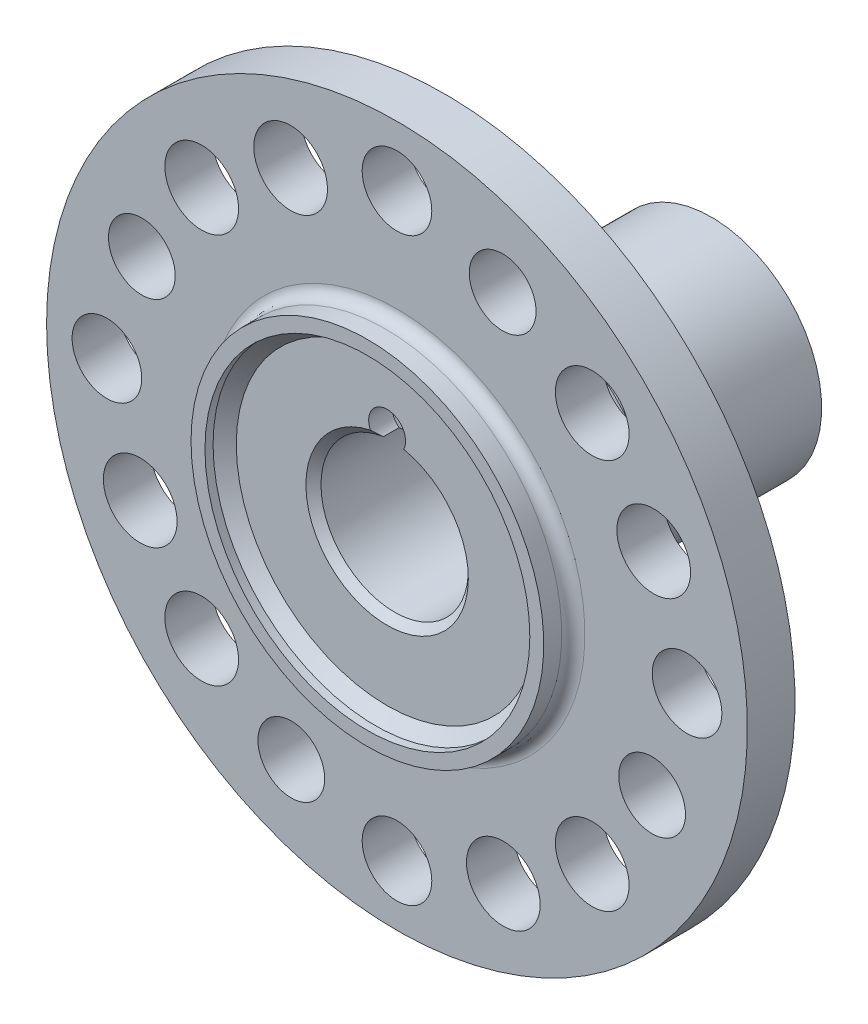
SolidWorks part; units mm, degrees
material "AISI 4130 Steel, normalized at 870C"
ref_plane "Front Plane" through (0, 0, 0) normal (0, 0, 1) x (1, 0, 0)
ref_plane "Top Plane" through (0, 0, 0) normal (0, 1, 0) x (1, 0, 0)
ref_plane "Right Plane" through (0, 0, 0) normal (1, 0, 0) x (0, 0, -1)
sketch "Sketch1" plane through (0, 0, 0) normal (1, 0, 0) x (0, 0, -1)
  line L0 (0.5, 19) -> (38, 19)
  line L1 (38, 19) -> (38, 18)
  line L2 (38, 18) -> (34.1, 14.1)
  line L3 (34.1, 14.1) -> (18.3, 14.1)
  line L4 (18.3, 14.1) -> (16.9, 12.7)
  line L5 (16.9, 12.7) -> (-16.6, 12.7)
  line L6 (-16.6, 12.7) -> (-17.9, 14)
  line L7 (-17.9, 14) -> (-17.9, 20.7)
  line L8 (0, 19.5) -> (0, 25.25)
  line L9 (0, 25.25) -> (-3.6, 28.85)
  line L10 (-3.6, 28.85) -> (-3.6, 35.7)
  line L11 (-3.6, 35.7) -> (-5.45, 35.7)
  line L12 (-7.45, 37.7) -> (-7.45, 38.8)
  line L13 (-7.45, 38.8) -> (-7.5, 38.8)
  line L14 (-8, 39.3) -> (-8, 60.4)
  line L15 (-8, 60.4) -> (-16.2, 60.4)
  line L16 (-16.2, 60.4) -> (-16.2, 32.4)
  line L17 (-18.2, 30.4) -> (-21.3, 30.4)
  line L18 (-21.3, 30.4) -> (-21.3, 29.9)
  line L19 (-23.3, 27.9) -> (-27.5, 27.9)
  line L20 (-27.5, 27.9) -> (-27.5, 25.3)
  line L21 (-27.5, 25.3) -> (-22.3, 25.3)
  line L22 (-20.3, 23.3) -> (-20.3, 21.7)
  line L23 (-20.3, 21.7) -> (-18.9, 21.7)
  line L25 (0, 0) -> (-74.9273, 0) construction
  arc A0 (0.5, 19) -> (0, 19.5) centre (0.5, 19.5) cw
  arc A1 (-5.45, 35.7) -> (-7.45, 37.7) centre (-5.45, 37.7) cw
  arc A2 (-7.5, 38.8) -> (-8, 39.3) centre (-7.5, 39.3) cw
  arc A3 (-22.3, 25.3) -> (-20.3, 23.3) centre (-22.3, 23.3) cw
  arc A4 (-21.3, 29.9) -> (-23.3, 27.9) centre (-23.3, 29.9) cw
  arc A5 (-16.2, 32.4) -> (-18.2, 30.4) centre (-18.2, 32.4) cw
  arc A6 (-18.9, 21.7) -> (-17.9, 20.7) centre (-18.9, 20.7) cw
  point P30 (0, 19)
  point P39 (-21.3, 27.9)
  dimension "D25" = 0.5
  dimension "D26" = 2
  dimension "D27" = 0.5
  dimension "D28" = 2
  dimension "D29" = 1
  dimension "D1" = 120.8
  dimension "D2" = 38
  dimension "D3" = 1
  dimension "D4" = 28.2
  dimension "D5" = 45
  dimension "D6" = 15.8
  dimension "D7" = 25.4
  dimension "D8" = 38
  dimension "D9" = 50.5
  dimension "D10" = 3.6
  dimension "D11" = 71.4
  dimension "D12" = 0.55
  dimension "D13" = 77.6
  dimension "D14" = 4.4
  dimension "D15" = 8.2
  dimension "D16" = 55.8
  dimension "D17" = 60.8
  dimension "D18" = 65.5
  dimension "D19" = 6.2
  dimension "D20" = 28
  dimension "D21" = 2.6
  dimension "D22" = 9.6
  dimension "D23" = 7.2
  dimension "D24" = 43.4
revolve "Revolve1" add sketch "Sketch1" angle 360 about L25
sketch "Sketch11" plane through (0, 0, 0) normal (0, 0, 1) x (1, 0, 0)
  circle A0 centre (0, 50) radius 6
  circle A1 centre (50, 0) radius 6
  circle A2 centre (0, -50) radius 6
  circle A3 centre (-50, 0) radius 6
  point P12 (0, 0)
  dimension "D1" = 12
  dimension "D3" = 4
  dimension "D2" = 50
extrude "Cut-Extrude4" cut sketch "Sketch11" along normal through all
sketch "Sketch2" plane through (0, 0, 0) normal (1, 0, 0) x (0, 0, -1)
  line L0 (-23.9376, 50) -> (16.7376, 50) construction
  line L1 (-46.2, 44.2) -> (-8, 44.2) construction
  line L2 (-8, -60.4) -> (-8, 60.4) construction
  line L3 (-8, 58.75) -> (-8, 55.8)
  line L4 (-46.2, 55.8) -> (-8, 55.8)
  line L5 (-8, 44.2) -> (-8, 41.25) construction
  line L6 (-46.2, 55.8) -> (-46.2, 50)
  line L7 (-8, 58.75) -> (-5.5, 58.75)
  line L8 (-5.5, 58.75) -> (-3.6, 56.9)
  line L9 (-3.6, 56.9) -> (-3.6, 50)
  line L10 (-5.5, 41.25) -> (-3.6, 43.1) construction
  line L11 (-8, 41.25) -> (-5.5, 41.25) construction
  line L13 (-46.2, 50) -> (-3.6, 50)
  line L14 (-3.6, 50) -> (-3.6, 43.1) construction
  line L15 (-46.2, 50) -> (-46.2, 44.2) construction
  point P15 (-3.6, 50)
  dimension "D1" = 50
  dimension "D3" = 17.5
  dimension "D4" = 11.6
  dimension "D6" = 13.8
  dimension "D7" = 2.5
revolve "Revolve3" [suppressed] add sketch "Sketch2" angle 360 about L0
pattern_circular "CirPattern2" [suppressed] count 4 over 360 of bodies 102
sketch "Sketch4" plane through (0, 0, 0) normal (1, 0, 0) x (0, 0, -1)
  line L0 (-7, 60.4832) -> (-7, 39.9952)
  line L1 (-7, 39.9952) -> (12.4061, 39.9952)
  line L2 (12.4061, 39.9952) -> (12.4061, 60.4832)
  line L3 (12.4061, 60.4832) -> (-7, 60.4832)
  line L4 (-8, -60.4) -> (-8, 60.4) construction
  line L5 (0, 0) -> (50.228, 0) construction
  dimension "D1" = 1
revolve "LatheTrimBolts" [suppressed] cut sketch "Sketch4" angle 360 about L5
sketch "Sketch5" plane through (0, 0, 0) normal (1, 0, 0) x (0, 0, -1)
  line L0 (-16.2, 60.4) -> (-16.2, -60.4) construction
  line L1 (-28.2, 70.4741) -> (-61.4144, 70.4741)
  line L2 (-28.2, 70.4741) -> (-28.2, 34.279)
  line L3 (-28.2, 34.279) -> (-61.4144, 34.279)
  line L4 (-61.4144, 70.4741) -> (-61.4144, 34.279)
  line L5 (-1.1501, 0) -> (-66.0136, 0) construction
  dimension "D1" = 12
revolve "LatheTrimBolts2" [suppressed] cut sketch "Sketch5" angle 360 about L5
sketch "Sketch7" plane through (0, 0, 0) normal (1, 0, 0) x (0, 0, -1)
  line L0 (-19.9, 28) -> (-17.9, 26)
  line L1 (-17.9, 26) -> (-17.9, 0)
  line L2 (-21.3, 28) -> (-21.3, 34.5114)
  line L3 (-17.9, 0) -> (-30.1633, 0)
  line L4 (-30.1633, 0) -> (-30.1633, 25.3)
  line L5 (0, 0) -> (-41.9984, 0) construction
  line L6 (-17.9, 20.7) -> (-17.9, -20.7) construction
  line L7 (-19.9, 28) -> (-21.3, 28)
  line L8 (-30.1633, 28) -> (-30.1633, 25.3)
  line L9 (-21.3, 34.5114) -> (-30.1633, 34.5114)
  line L10 (-30.1633, 34.5114) -> (-30.1633, 28)
  line L11 (-21.3, 29.9) -> (-21.3, -29.9) construction
  point P13 (-17.9, 28)
  dimension "D2" = 0
  dimension "D4" = 56
revolve "LatheCutPocket" cut sketch "Sketch7" angle 360 about L5
sketch "Sketch8" plane through (0, 0, 8) normal (0, 0, 1) x (1, 0, 0)
  line L0 (0, 0) -> (0, 65.1382) construction
  line L1 (0, 0) -> (18.2157, 43.9767) construction
  circle A0 centre (18.2157, 43.9767) radius 6.75
  circle A1 centre (43.9767, -18.2157) radius 6.75
  circle A2 centre (-18.2157, -43.9767) radius 6.75
  circle A3 centre (-43.9767, 18.2157) radius 6.75
  point P14 (0, 0)
  dimension "D3" = 13.5
  dimension "D1" = 22.5
  dimension "D2" = 47.6
  dimension "D4" = 4
hole_wizard "1/2-20 Tapped Hole1" positions "Sketch13" profile "Sketch12" tap size "1/2-20" standard "ANSI Inch" end condition through all
sketch "Sketch13" plane through (0, 0, 16.2) normal (0, 0, 1) x (1, 0, 0)
  point P0 (18.2157, 43.9767)
  point P2 (43.9767, -18.2157)
  point P4 (-18.2157, -43.9767)
  point P6 (-43.9767, 18.2157)
sketch "Sketch12" plane through (18.2157, 43.9767, 16.2) normal (1, 0, 0) x (0, -1, 0)
  line L0 (0, 0) -> (0, 54.2)
  line L1 (0, 54.2) -> (5.7544, 54.2)
  line L2 (5.7544, 54.2) -> (5.7544, 0)
  line L5 (5.7544, 0) -> (0, 0)
  line L11 (0, -6.35) -> (0, 107.95) construction
  dimension "Thru Tap Drill Dia." = 11.5087
  dimension "Thru Tap Drill Depth" = 54.2
cosmetic thread "Hole Thread1" parameters "D2"=12.7
cosmetic thread "Hole Thread2" parameters "D2"=12.7
cosmetic thread "Hole Thread3" parameters "D2"=12.7
cosmetic thread "Hole Thread4" parameters "D2"=12.7
sketch "Sketch14" plane through (0, 0, 0) normal (0, 0, 1) x (1, 0, 0)
  line L0 (0, 0) -> (0, 70.9536) construction
  line L1 (0, 0) -> (33.6583, 33.6583) construction
  line L2 (0, 0) -> (44.2541, 18.3307) construction
  line L3 (0, 0) -> (18.2157, 43.9767) construction
  circle A0 centre (33.6583, 33.6583) radius 6.35
  circle A1 centre (44.2541, 18.3307) radius 6.35
  circle A2 centre (33.6583, -33.6583) radius 6.35
  circle A3 centre (18.3307, -44.2541) radius 6.35
  circle A4 centre (-33.6583, -33.6583) radius 6.35
  circle A5 centre (-44.2541, -18.3307) radius 6.35
  circle A6 centre (-33.6583, 33.6583) radius 6.35
  circle A7 centre (-18.3307, 44.2541) radius 6.35
  point P22 (0, 0)
  dimension "D3" = 12.7
  dimension "D1" = 45
  dimension "D2" = 22.5
  dimension "D4" = 4
extrude "Cut-Extrude5" cut sketch "Sketch14" along normal through all
sketch "Sketch15" plane through (0, 0, 17.9) normal (0, 0, 1) x (1, 0, 0)
  circle A0 centre (0, 15.075) radius 3.175
  dimension "D1" = 6.35
  dimension "D2" = 15.075
extrude "Cut-Extrude6" cut sketch "Sketch15" against normal blind 4
